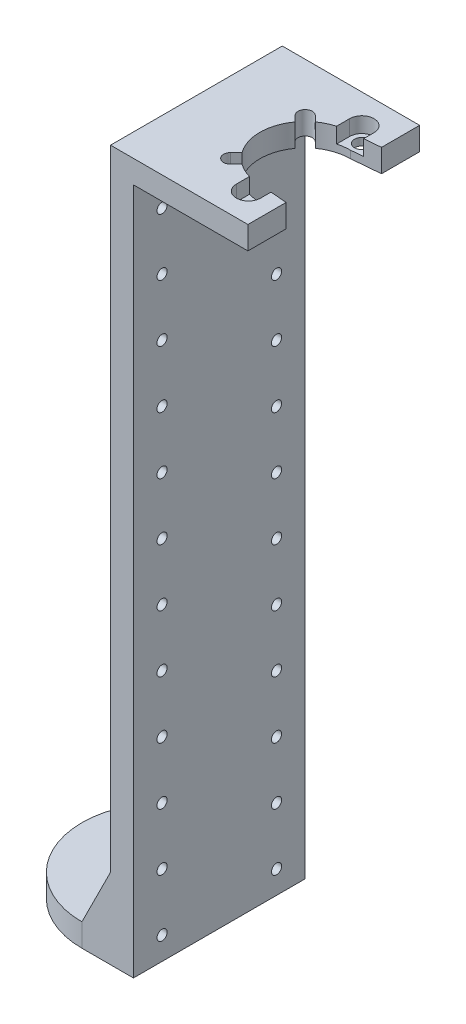
SolidWorks part; units mm, degrees
material "Copper"
ref_plane "Front Plane" through (0, 0, 0) normal (0, 0, 1) x (1, 0, 0)
ref_plane "Top Plane" through (0, 0, 0) normal (0, 1, 0) x (1, 0, 0)
ref_plane "Right Plane" through (0, 0, 0) normal (1, 0, 0) x (0, 0, -1)
sketch "Sketch1" plane through (0, 0, 0) normal (0, 0, 1) x (1, 0, 0)
  line L0 (0, 0) -> (0, 120)
  line L1 (0, 120) -> (24, 120)
  line L2 (24, 120) -> (24, 116)
  line L3 (24, 116) -> (4, 116)
  line L4 (4, 116) -> (4, -4)
  line L5 (4, -4) -> (-20, -4)
  line L6 (-20, -4) -> (-20, 0)
  line L7 (-20, 0) -> (0, 0)
  dimension "D1" = 24
  dimension "D2" = 24
  dimension "D3" = 20
  dimension "D4" = 4
  dimension "D5" = 4
  dimension "D6" = 120
  dimension "D7" = 120
extrude "BracketMainBody" add sketch "Sketch1" along normal mid plane 30
sketch "M4_thruHole" plane through (0, -4, 0) normal (0, -1, 0) x (1, 0, 0)
  line L0 (-20, 15) -> (-20, -15) construction
  circle A0 centre (-10, 0) radius 2.4
  dimension "D1" = 4.8
  dimension "D2" = 10
  dimension "D3" = 10
sketch "SQUIDcutouts" plane through (0, 0, 0) normal (0, 1, 0) x (1, 0, 0)
  line L0 (24, -15) -> (24, 15) construction
  line L3 (0, -15) -> (0, 15) construction
  line L4 (24, 0) -> (4, 0) construction
  line L5 (12.6003, 4.6319) -> (11.6161, 5.6161)
  line L6 (13.3839, 7.3839) -> (14.3681, 6.3997)
  line L7 (11.6161, -5.6161) -> (12.6003, -4.6319)
  line L9 (13.3839, -7.3839) -> (14.3681, -6.3997)
  circle A0 centre (19, -9.9) radius 1.3
  circle A1 centre (19, 9.9) radius 1.3
  arc A2 (12.6003, 4.6319) -> (12.6003, -4.6319) centre (19, 0) ccw
  arc A3 (13.3839, 7.3839) -> (11.6161, 5.6161) centre (12.5, 6.5) ccw
  arc A4 (11.6161, -5.6161) -> (13.3839, -7.3839) centre (12.5, -6.5) ccw
  arc A5 (14.3681, -6.3997) -> (14.3681, 6.3997) centre (19, 0) ccw
  dimension "D1" = 5
  dimension "D3" = 2.6
  dimension "D4" = 2.6
  dimension "D9" = 15.8
  dimension "D12" = 2.5
  dimension "D15" = 2.5
  dimension "D18" = 1.3919
  dimension "D2" = 9.9
  dimension "D5" = 5
  dimension "D6" = 9.9
  dimension "D7" = 5
  dimension "D10" = 6.5
  dimension "D11" = 12.5
  dimension "D13" = 6.5
  dimension "D14" = 12.5
  dimension "D16" = 1.3919
  dimension "D17" = 1.3919
  dimension "D19" = 7.9424
extrude "CutExtrude_SQUIDcutouts" cut sketch "SQUIDcutouts" against normal through all from surface contours A0 | A1 | A5 L6 A3 L5 A2 L7 A4 L9 starting at face at (12, 120, 0)
sketch "champhers" plane through (0, 120, 0) normal (0, 1, 0) x (1, 0, 0)
  line L0 (24, 8.3374) -> (24, 6.1164)
  line L1 (24, 6.1164) -> (24, 15) construction
  line L2 (24, 8.3374) -> (19, 7.9)
  line L4 (30.1328, 0) -> (13.0253, 0) construction
  line L5 (24, -6.1164) -> (19, -7.9)
  line L6 (24, -8.3374) -> (19, -7.9)
  line L7 (24, -8.3374) -> (24, -6.1164)
  line L9 (19, 7.9) -> (24, 6.1164)
  arc A0 (14.3681, -6.3997) -> (14.3681, 6.3997) centre (19, 0) ccw construction
  dimension "D2" = 85
extrude "Cut-Extrude7" [suppressed] cut sketch "champhers" against normal through all
sketch "Sketch13" plane through (0, 120, 0) normal (0, 1, 0) x (1, 0, 0)
  line L0 (19, 9.9) -> (19, -9.9) construction
  line L5 (21.1241, 9.9) -> (21.1241, -9.9)
  line L6 (16.8759, 9.9) -> (16.8759, -9.9)
  arc A3 (21.1241, 9.9) -> (16.8759, 9.9) centre (19, 9.9) ccw
  arc A4 (16.8759, -9.9) -> (21.1241, -9.9) centre (19, -9.9) ccw
  point P3 (19, 0)
  dimension "D1" = 19.8
  dimension "D2" = 2.1241
ref_plane "M2CounterBore_offsetTopPlane" through (0, 117.3, 0) normal (0, 1, 0) x (1, 0, 0)
hole_wizard "M4 Clearance Hole1" positions "3DSketch1" profile "Sketch18" hole size "M4" standard "ANSI Metric" end condition up to next
sketch3d "3DSketch1"
  point P0 (-10, -4, 0)
sketch "Sketch18" plane through (-10, -4, 0) normal (1, 0, 0) x (0, 0, -1)
  line L0 (0, 0) -> (0, 4)
  line L1 (0, 4) -> (2.25, 4)
  line L2 (2.25, 4) -> (2.25, 0)
  line L5 (2.25, 0) -> (0, 0)
  line L11 (0, -6.35) -> (0, 107.95) construction
  dimension "Thru Hole Dia." = 4.5
  dimension "Thru Hole Depth" = 4
extrude "Cut-Extrude12" cut sketch "champhers<2>" against normal up to next
sketch "champhers<2>" plane through (0, 120, 0) normal (0, 1, 0) x (1, 0, 0) same geometry as "champhers"
fillet "Fillet11" radius 15 1 edges at (-20, -2, -15)
fillet "Fillet12" radius 15 1 edges at (-20, -2, 15)
fillet "Fillet13" [suppressed] radius 7.54
sketch "Sketch24" plane through (0, 0, 0) normal (1, 0, 0) x (0, 0, -1)
  line L0 (0, 0) -> (0, 120) construction
  line L1 (-15, 120) -> (15, 120) construction
  point P0 (10, 110)
  dimension "D1" = 10
  dimension "D2" = 10
hole_wizard "#2-56 Tapped Hole1" positions "3DSketch5" profile "Sketch25" tap size "#2-56" standard "ANSI Inch" end condition up to next
sketch3d "3DSketch5"
  line L0 (0, 0, 0) -> (0, 120, 0) construction
  line L1 (0, 120, 15) -> (0, 120, -15) construction
  point P4 (0, 110, -10)
  dimension "D1" = 10
  dimension "D2" = 10
sketch "Sketch25" plane through (0, 110, -10) normal (0, 1, 0) x (0, 0, 1)
  line L0 (0, 0) -> (0, 4.001)
  line L1 (0, 4.001) -> (0.889, 4.001)
  line L2 (0.889, 4.001) -> (0.889, 0)
  line L5 (0.889, 0) -> (0, 0)
  line L11 (0, -6.35) -> (0, 107.95) construction
  dimension "Thru Tap Drill Dia." = 1.778
  dimension "Thru Tap Drill Depth" = 4.001
cosmetic thread "Hole Thread2" parameters "D2"=2.1844
pattern_linear "LPattern3" count 12 spacing 10 along (0, -1, 0) count 2 spacing 20 along (0, 0, 1) of "#2-56 Tapped Hole1"
cosmetic thread "Hole Thread3" parameters "D2"=2.1844
cosmetic thread "Hole Thread4" parameters "D2"=2.1844
cosmetic thread "Hole Thread5" parameters "D2"=2.1844
cosmetic thread "Hole Thread6" parameters "D2"=2.1844
cosmetic thread "Hole Thread7" parameters "D2"=2.1844
cosmetic thread "Hole Thread8" parameters "D2"=2.1844
cosmetic thread "Hole Thread9" parameters "D2"=2.1844
cosmetic thread "Hole Thread10" parameters "D2"=2.1844
cosmetic thread "Hole Thread11" parameters "D2"=2.1844
cosmetic thread "Hole Thread12" parameters "D2"=2.1844
cosmetic thread "Hole Thread13" parameters "D2"=2.1844
cosmetic thread "Hole Thread14" parameters "D2"=2.1844
cosmetic thread "Hole Thread15" parameters "D2"=2.1844
cosmetic thread "Hole Thread16" parameters "D2"=2.1844
cosmetic thread "Hole Thread17" parameters "D2"=2.1844
cosmetic thread "Hole Thread18" parameters "D2"=2.1844
cosmetic thread "Hole Thread19" parameters "D2"=2.1844
cosmetic thread "Hole Thread20" parameters "D2"=2.1844
cosmetic thread "Hole Thread21" parameters "D2"=2.1844
cosmetic thread "Hole Thread22" parameters "D2"=2.1844
cosmetic thread "Hole Thread23" parameters "D2"=2.1844
cosmetic thread "Hole Thread24" parameters "D2"=2.1844
cosmetic thread "Hole Thread25" parameters "D2"=2.1844
extrude "Cut-Extrude14" cut sketch "Sketch13" against normal up to surface (2.7 mm away) contours L5 A4 L6 A3 up to plane "M2CounterBore_offsetTopPlane"
sketch "Sketch28" plane through (0, 0, -15) normal (0, 0, -1) x (-1, 0, 0)
  line L0 (-24, 120) -> (-24, 116)
  line L1 (-24, 120) -> (0, 120)
  line L2 (0, 120) -> (0, 108)
  line L3 (0, 120) -> (0, 0) construction
  line L4 (0, 108) -> (-4, 108)
  line L5 (-4, -4) -> (-4, 116) construction
  line L7 (-4, 116) -> (-24, 116) construction
  line L8 (-12, 116) -> (-4, 108)
  line L9 (-24, 116) -> (-12, 116)
  dimension "D1" = 12
  dimension "D2" = 24
  dimension "D3" = 4
  dimension "D4" = 12
sketch "Sketch29" plane through (0, 0, 15) normal (0, 0, 1) x (1, 0, 0)
  line L0 (24, 120) -> (0, 120)
  line L1 (24, 120) -> (0, 120) construction
  line L2 (0, 120) -> (0, 108)
  line L3 (0, 120) -> (0, 0) construction
  line L4 (0, 108) -> (4, 108)
  line L5 (4, -4) -> (4, 116) construction
  line L7 (4, 116) -> (24, 116) construction
  line L8 (12, 116) -> (4, 108)
  line L9 (24, 120) -> (24, 116)
  line L10 (24, 116) -> (12, 116)
  dimension "D1" = 24
  dimension "D2" = 12
  dimension "D3" = 4
  dimension "D4" = 12
sketch "Sketch30" plane through (0, 0, 15) normal (0, 0, 1) x (1, 0, 0)
  line L0 (-5, 0) -> (0, 0)
  line L1 (-20, 0) -> (0, 0) construction
  line L2 (0, 0) -> (0, 10)
  line L3 (0, 0) -> (0, 120) construction
  line L4 (0, 10) -> (-5, 0)
  dimension "D1" = 10
  dimension "D2" = 5
extrude "Boss-Extrude3" add sketch "Sketch30" against normal blind 2
sketch "Sketch31" plane through (0, 0, -15) normal (0, 0, -1) x (-1, 0, 0)
  line L0 (0, 10) -> (0, 0)
  line L1 (0, 120) -> (0, 0) construction
  line L2 (0, 0) -> (5, 0)
  line L3 (0, 0) -> (5, 0) construction
  line L4 (5, 0) -> (0, 10)
  dimension "D1" = 10
  dimension "D2" = 5
extrude "Boss-Extrude4" add sketch "Sketch31" against normal blind 2
fillet "Fillet17" radius 3.5 1 edges at (-2.5, 0, -13)
fillet "Fillet18" radius 3.5 1 edges at (-2.5, 0, 13)
sketch "Sketch32" plane through (0, 116, 0) normal (0, -1, 0) x (1, 0, 0)
  circle A0 centre (19, 0) radius 13.5
  dimension "D1" = 27
extrude "Boss-Extrude5" [suppressed] add sketch "Sketch32" along normal blind 110
